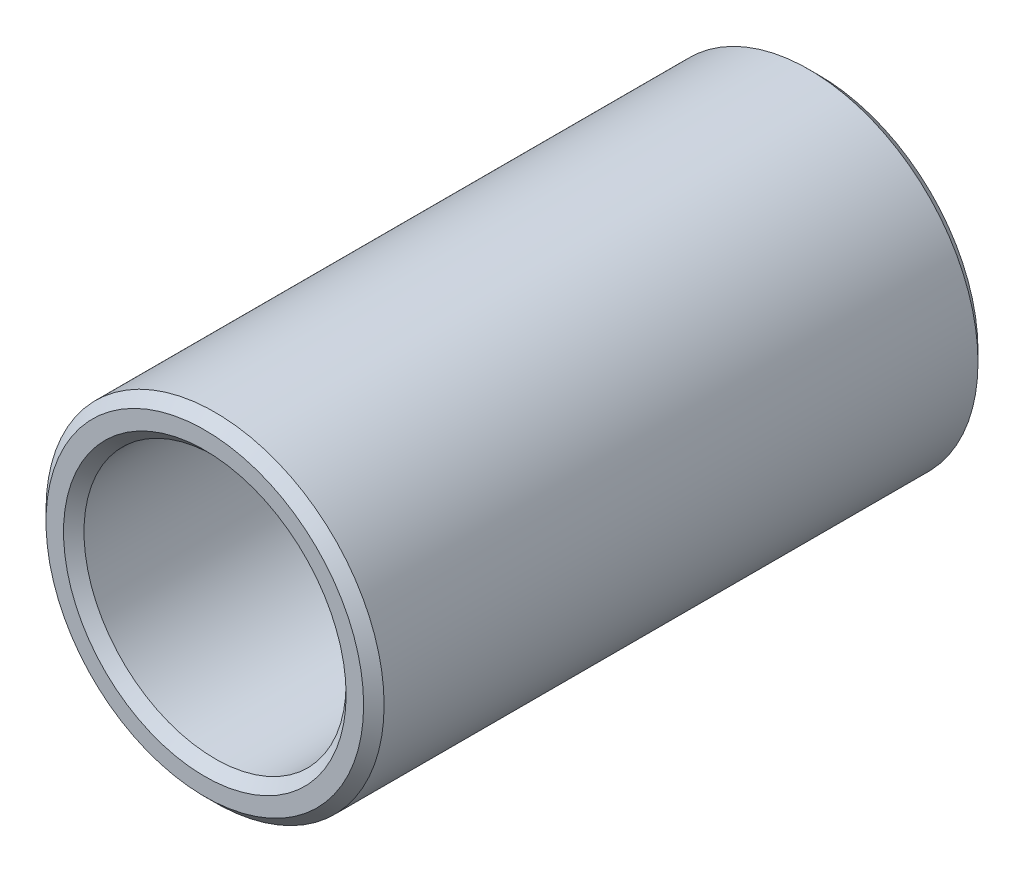
SolidWorks part; units mm, degrees
material "ABS"
ref_plane "Front Plane" through (0, 0, 0) normal (0, 0, 1) x (1, 0, 0)
ref_plane "Top Plane" through (0, 0, 0) normal (0, 1, 0) x (1, 0, 0)
ref_plane "Right Plane" through (0, 0, 0) normal (1, 0, 0) x (0, 0, -1)
sketch "Sketch1" plane through (0, 0, 0) normal (0, 0, 1) x (1, 0, 0)
  circle A0 centre (0, 0) radius 4.1275
  circle A1 centre (0, 0) radius 3.2
  dimension "D1" = 6.4
  dimension "D2" = 8.255
extrude "Boss-Extrude1" add sketch "Sketch1" along normal blind 15
chamfer "Chamfer1" distance 0.25 angle 45 4 edges at (3.2, 0, 15) (4.1275, 0, 15) (3.2, 0, 0) (4.1275, 0, 0)
